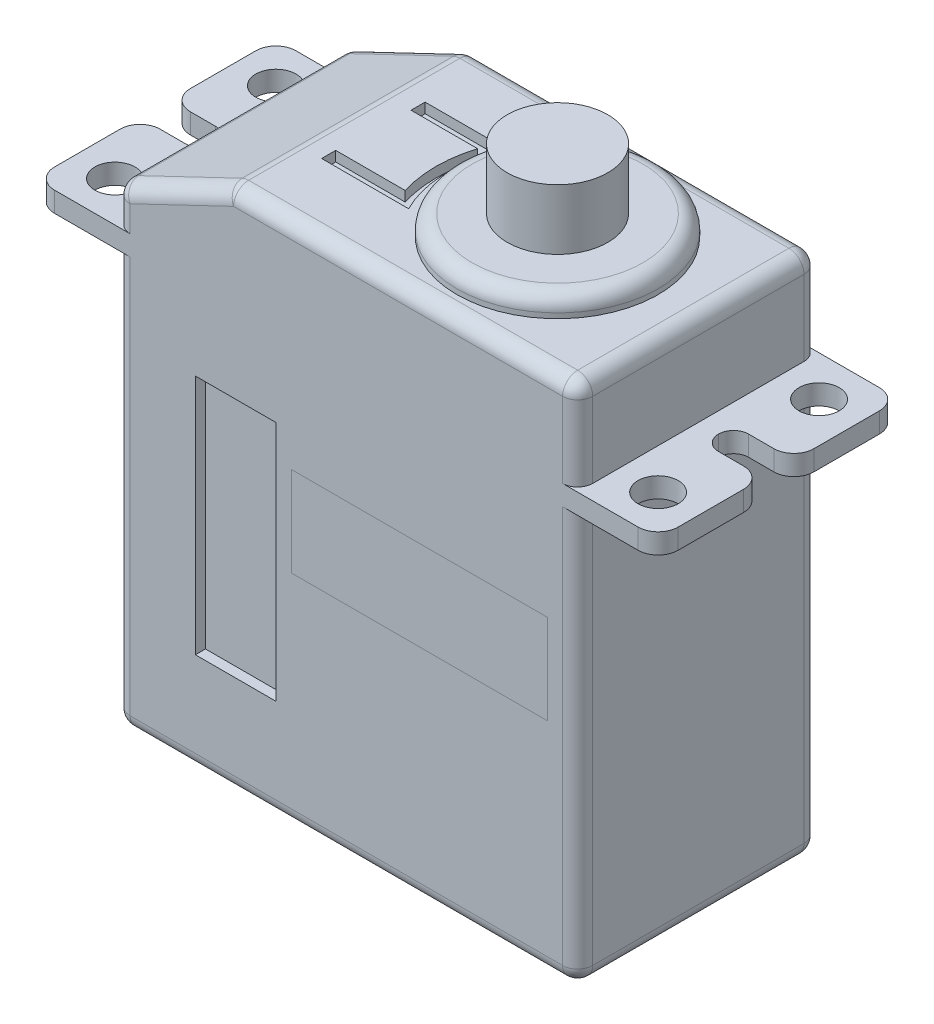
SolidWorks part; units mm, degrees
ref_plane "Front Plane" through (0, 0, 0) normal (0, 0, 1) x (1, 0, 0)
ref_plane "Top Plane" through (0, 0, 0) normal (0, 1, 0) x (1, 0, 0)
ref_plane "Right Plane" through (0, 0, 0) normal (1, 0, 0) x (0, 0, -1)
sketch "Sketch1" plane through (0, 0, 0) normal (0, 0, 1) x (1, 0, 0)
  line L1 (0, 0) -> (23, 0)
  line L2 (0, 0) -> (0, 26)
  line L3 (0, 26) -> (23, 26)
  line L4 (23, 0) -> (23, 26)
  dimension "D1" = 26
  dimension "D2" = 23
extrude "Boss-Extrude1" add sketch "Sketch1" along normal blind 12
sketch "Sketch2" plane through (0, 0, 12) normal (0, 0, 1) x (1, 0, 0)
  line L0 (5.726, 26) -> (0, 23.2609)
  line L1 (23, 26) -> (0, 26) construction
  line L2 (0, 26) -> (0, 0) construction
  line L3 (0, 23.2609) -> (0, 26)
  line L4 (0, 26) -> (5.726, 26)
extrude "Cut-Extrude1" cut sketch "Sketch2" against normal blind 12
sketch "Sketch3" plane through (0, 0, 0) normal (-1, 0, 0) x (0, 0, 1)
  line L0 (0, 23.2609) -> (0, 0) construction
  line L1 (0, 21.5) -> (12, 21.5)
  line L2 (0, 21.5) -> (0, 20.5)
  line L3 (0, 20.5) -> (12, 20.5)
  line L4 (12, 21.5) -> (12, 20.5)
  line L5 (12, 23.2609) -> (12, 0) construction
  line L6 (12, 0) -> (0, 0) construction
  dimension "D1" = 1
  dimension "D2" = 20.5
extrude "Boss-Extrude2" add sketch "Sketch3" along normal blind 4 and the other way blind 27
sketch "Sketch5" plane through (0, 21.5, 0) normal (0, 1, 0) x (1, 0, 0)
  line L0 (0, 0) -> (-4, 0) construction
  line L1 (27, 0) -> (23, 0) construction
  line L2 (0, -12) -> (-4, -12) construction
  line L3 (27, -12) -> (23, -12) construction
  circle A0 centre (-2, -10) radius 1
  circle A1 centre (-2, -2) radius 1
  circle A2 centre (25, -2) radius 1
  circle A3 centre (25, -10) radius 1
  point P10 (-2, 0)
  point P13 (25, 0)
  dimension "D5" = 2
  dimension "D1" = 2
  dimension "D2" = 2
  dimension "D3" = 2
  dimension "D4" = 2
extrude "Cut-Extrude2" cut sketch "Sketch5" against normal blind 5
sketch "Sketch6" plane through (0, 21.5, 0) normal (0, 1, 0) x (1, 0, 0)
  line L0 (-4, -12) -> (-4, 0) construction
  line L1 (-4, -5.25) -> (-1, -5.25)
  line L2 (-4, -5.25) -> (-4, -6.75)
  line L3 (-4, -6.75) -> (-1, -6.75)
  line L4 (-1, -5.25) -> (-1, -6.75)
  line L5 (27, -12) -> (27, 0) construction
  line L6 (27, -5.25) -> (24, -5.25)
  line L7 (27, -5.25) -> (27, -6.75)
  line L8 (27, -6.75) -> (24, -6.75)
  line L9 (24, -5.25) -> (24, -6.75)
  point P12 (-4, -6)
  point P13 (-1, -6)
  point P14 (27, -6)
  point P15 (24, -6)
  dimension "D1" = 1.5
  dimension "D2" = 1.5
  dimension "D3" = 3
  dimension "D4" = 3
extrude "Cut-Extrude3" cut sketch "Sketch6" against normal blind 5
fillet "Fillet1" radius 1 8 edges at (-4, 21, 5.25) (27, 21, 0) (27, 21, 5.25) (27, 21, 6.75) (27, 21, 12) (-4, 21, 12) (-4, 21, 6.75) (-4, 21, 0)
fillet "Fillet2" radius 0.75 4 edges at (-1, 21, 6.75) (-1, 21, 5.25) (24, 21, 6.75) (24, 21, 5.25)
sketch "Sketch7" plane through (0, 26, 0) normal (0, 1, 0) x (1, 0, 0)
  line L0 (23, -12) -> (23, 0) construction
  line L1 (23, -12) -> (23, 0) construction
  circle A0 centre (16, -6) radius 5
  point P4 (23, -6)
  dimension "D1" = 10
  dimension "D2" = 7
extrude "Boss-Extrude3" add sketch "Sketch7" along normal blind 1
sketch "Sketch8" plane through (0, 26, 0) normal (0, 1, 0) x (1, 0, 0)
  line L0 (11.1019, -3.5) -> (6.9174, -3.5)
  line L1 (6.9174, -3.5) -> (6.9174, -4.2)
  line L2 (6.9174, -4.2) -> (10.2291, -4.2)
  line L3 (6.7735, -8.5) -> (11.1019, -8.5)
  line L4 (6.7735, -8.5) -> (6.7735, -7.8)
  line L5 (6.7735, -7.8) -> (10.2291, -7.8)
  line L6 (23, 0) -> (5.726, 0) construction
  line L7 (23, -12) -> (5.726, -12) construction
  arc A0 (11.1019, -3.5) -> (11.1019, -8.5) centre (16, -6) ccw
  arc A1 (10.2291, -4.2) -> (10.2291, -7.8) centre (16, -6) ccw
  dimension "D1" = 0.7
  dimension "D2" = 0.7
  dimension "D3" = 3.5
  dimension "D4" = 3.5
extrude "Cut-Extrude4" cut sketch "Sketch8" against normal blind 0.5
fillet "Fillet3" radius 0.75 20 edges at (23, 0, 6) (11.5, 0, 12) (0, 0, 6) (0, 22.3805, 0) (0, 22.3805, 12) (0, 10.25, 12) (0, 10.25, 0) (11.5, 0, 0) (23, 26, 6) (23, 23.75, 12) (23, 10.25, 12) (23, 10.25, 0) (23, 23.75, 0) (16, 27, 11) (14.363, 26, 12) (2.863, 24.6305, 12) (0, 23.2609, 6) (2.863, 24.6305, 0) (5.726, 26, 6) (14.363, 26, 0)
sketch "Sketch9" plane through (0, 0, 12) normal (0, 0, 1) x (1, 0, 0)
  line L0 (22.25, 0) -> (0.75, 0) construction
  line L1 (4, 17) -> (8, 17)
  line L2 (4, 17) -> (4, 5)
  line L3 (4, 5) -> (8, 5)
  line L4 (8, 17) -> (8, 5)
  line L5 (0, 0.75) -> (0, 20.5) construction
  dimension "D1" = 12
  dimension "D2" = 4
  dimension "D3" = 5
  dimension "D4" = 4
extrude "Cut-Extrude5" cut sketch "Sketch9" against normal blind 0.5
sketch "Sketch10" plane through (0, 27, 0) normal (0, 1, 0) x (1, 0, 0)
  circle A0 centre (16, -6) radius 2.5
  dimension "D1" = 5
extrude "Boss-Extrude4" add sketch "Sketch10" along normal blind 3
sketch "Sketch11" plane through (0, 0, 12) normal (0, 0, 1) x (1, 0, 0)
  line L1 (8.7709, 15.3612) -> (21.4934, 15.3612)
  line L2 (8.7709, 15.3612) -> (8.7709, 10.9063)
  line L3 (8.7709, 10.9063) -> (21.4934, 10.9063)
  line L4 (21.4934, 15.3612) -> (21.4934, 10.9063)
split line "Split Line1"
